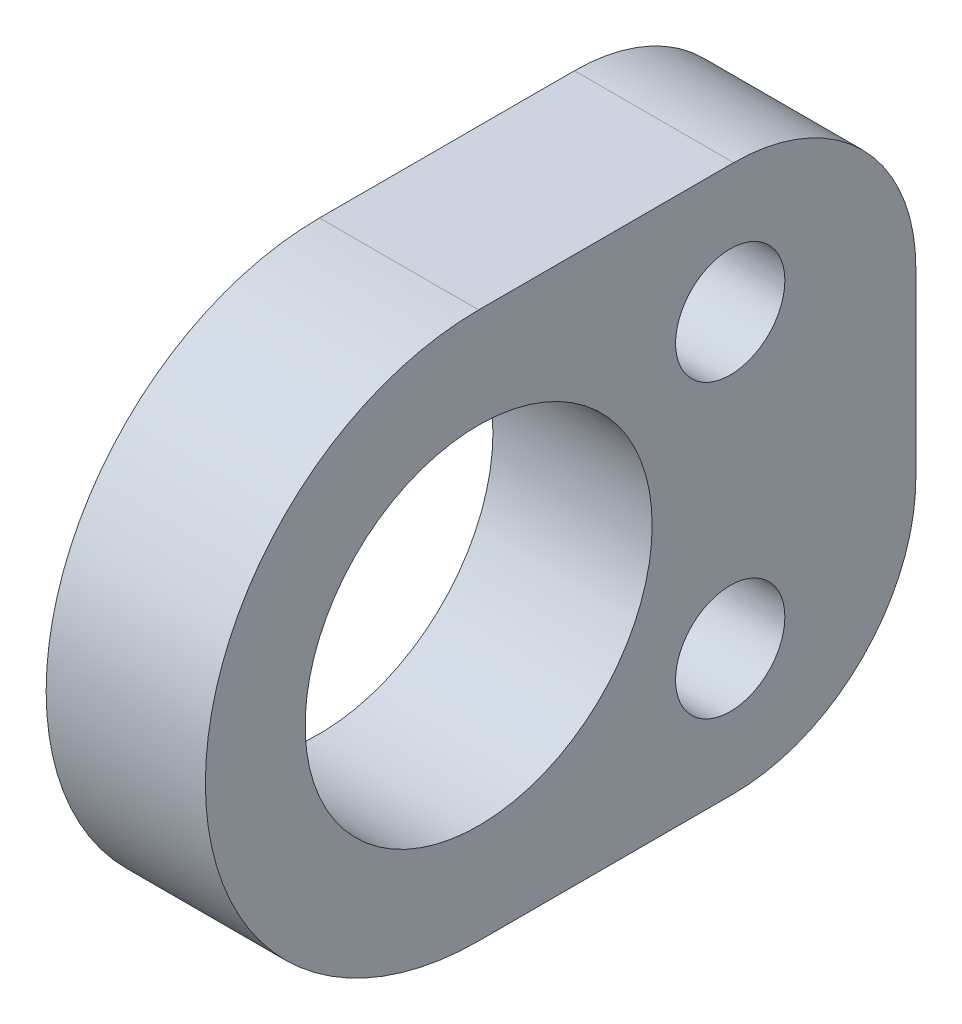
SolidWorks part; units mm, degrees
material "Plain Carbon Steel"
ref_plane "Front Plane" through (0, 0, 0) normal (0, 0, 1) x (1, 0, 0)
ref_plane "Top Plane" through (0, 0, 0) normal (0, 1, 0) x (1, 0, 0)
ref_plane "Right Plane" through (0, 0, 0) normal (1, 0, 0) x (0, 0, -1)
sketch "Sketch1" plane through (0, 0, 0) normal (1, 0, 0) x (0, 0, -1)
  line L0 (6.9051, 4) -> (6.9051, -4) construction
  line L1 (0, 7.5) -> (12, 7.5)
  line L2 (12, 7.5) -> (12, -7.5)
  line L3 (12, -7.5) -> (0, -7.5)
  arc A1 (6.9051, -4) -> (6.9051, 4) centre (0, 0) ccw construction
  circle A2 centre (6.9051, -4) radius 1.5
  circle A3 centre (6.9051, 4) radius 1.5
  circle A5 centre (0, 0) radius 4.7625
  arc A7 (0, 7.5) -> (0, -7.5) centre (0, 0) ccw
  point P21 (12, 0)
  dimension "D1" = 15
  dimension "D2" = 7.98
  dimension "D4" = 3
  dimension "D5" = 12
  dimension "D6" = 9.525
  dimension "D3" = 8
extrude "Boss-Extrude1" add sketch "Sketch1" along normal blind 4.37 contours A3 A2 region at (0, 7.254, -6)
fillet "Fillet1" radius 5 2 edges at (2.185, 7.5, -12) (2.185, -7.5, -12)
